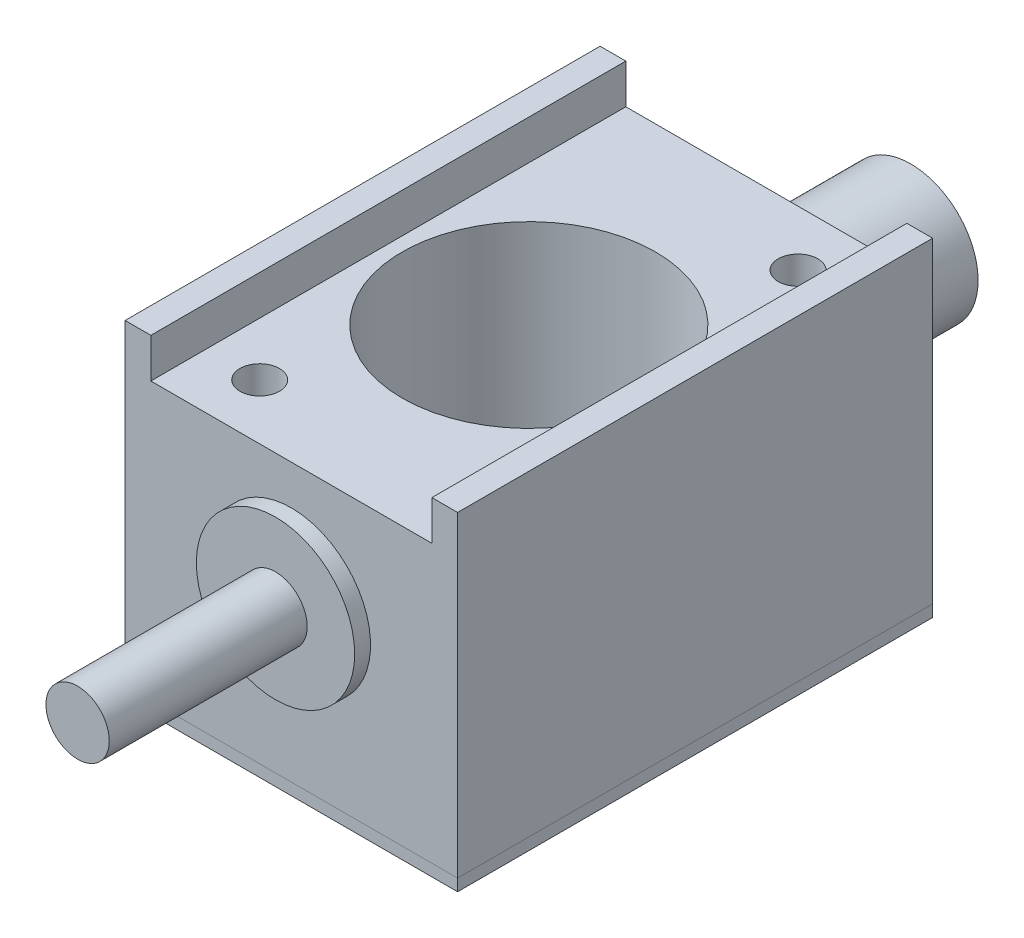
SolidWorks part; units mm, degrees
material "AISI 316 Annealed Stainless Steel Bar (SS)"
ref_plane "Front Plane" through (0, 0, 0) normal (0, 0, 1) x (1, 0, 0)
ref_plane "Top Plane" through (0, 0, 0) normal (0, 1, 0) x (1, 0, 0)
ref_plane "Right Plane" through (0, 0, 0) normal (1, 0, 0) x (0, 0, -1)
sketch "Sketch1" plane through (0, 0, 0) normal (0, 0, 1) x (1, 0, 0)
  line L1 (-21, -20) -> (21, -20)
  line L2 (-21, -20) -> (-21, 20)
  line L3 (-21, 20) -> (21, 20)
  line L4 (21, -20) -> (21, 20)
  line L5 (-21, -20) -> (21, 20) construction
  line L6 (-21, 20) -> (21, -20) construction
  point P0 (0, 0)
  dimension "D1" = 40
  dimension "D2" = 42
extrude "Boss-Extrude1" add sketch "Sketch1" along normal blind 60
sketch "Sketch2" plane through (0, 0, 60) normal (0, 0, 1) x (1, 0, 0)
  line L0 (21, -20) -> (21, 20) construction
  line L1 (-21, 20) -> (21, 20)
  line L2 (-21, 20) -> (-21, 15)
  line L3 (-21, 15) -> (21, 15)
  line L4 (21, 20) -> (21, 15)
  line L5 (17.75, 20) -> (17.75, 15)
  line L6 (-17.75, 20) -> (-17.75, 15)
  dimension "D1" = 5
  dimension "D2" = 3.25
  dimension "D3" = 3.25
extrude "Cut-Extrude1" cut sketch "Sketch2" against normal blind 60 contours L1 L6 L3 L5
sketch "Sketch3" plane through (0, 15, 0) normal (0, 1, 0) x (1, 0, 0)
  line L0 (-17.75, 0) -> (17.75, 0) construction
  circle A0 centre (0, -30) radius 16
  dimension "D1" = 32
  dimension "D2" = 30
extrude "Cut-Extrude2" cut sketch "Sketch3" against normal blind 40
sketch "Sketch4" plane through (0, 0, 0) normal (0, 0, -1) x (-1, 0, 0)
  circle A1 centre (0, 0) radius 8.5
  dimension "D2" = 17
extrude "Boss-Extrude2" add sketch "Sketch4" along normal blind 18.25
sketch "Sketch6" plane through (0, 0, 0) normal (0, 0, -1) x (-1, 0, 0)
  circle A0 centre (0, 0) radius 12.5
  dimension "D1" = 25
extrude "Boss-Extrude3" add sketch "Sketch6" along normal blind 2
sketch "Sketch7" plane through (0, 0, 60) normal (0, 0, 1) x (1, 0, 0)
  circle A0 centre (0, 0) radius 10
  dimension "D1" = 20
extrude "Boss-Extrude4" add sketch "Sketch7" along normal blind 2
sketch "Sketch8" plane through (0, 0, 62) normal (0, 0, 1) x (1, 0, 0)
  circle A0 centre (0, 0) radius 4
  dimension "D1" = 8
extrude "Boss-Extrude5" add sketch "Sketch8" along normal blind 25
sketch "Sketch9" plane through (0, 0, -18.25) normal (0, 0, -1) x (-1, 0, 0)
  circle A0 centre (0, 0) radius 2.5
  dimension "D1" = 5
extrude "Cut-Extrude6" cut sketch "Sketch9" against normal blind 32
sketch "Sketch10" plane through (0, -20, 0) normal (0, -1, 0) x (1, 0, 0)
  line L1 (-21, 60) -> (21, 60)
  line L2 (-21, 60) -> (-21, 0)
  line L3 (-21, 0) -> (21, 0)
  line L4 (21, 60) -> (21, 0)
  circle A0 centre (-11, 53) radius 2.5
  circle A1 centre (11, 7) radius 2.5
  circle A2 centre (0, 30) radius 11.2 construction
  circle A4 centre (0, 30) radius 6.75
  circle A5 centre (0, 40.7) radius 1.6
  circle A6 centre (0, 19.3) radius 1.6
  circle A7 centre (0, 30) radius 10.7 construction
  circle A8 centre (-11.2, 30) radius 1.55
  circle A9 centre (11.2, 30) radius 1.55
  dimension "D1" = 7
  dimension "D3" = 5
  dimension "D6" = 13.5
  dimension "D7" = 3.2
  dimension "D8" = 21.4
  dimension "D9" = 3.1
  dimension "D10" = 22.4
  dimension "D2" = 10
  dimension "D4" = 10
  dimension "D5" = 7
base flange "Base-Flange1" sketch "Sketch10" thickness 1.5 reverse thickness direction yes parameters "D1"=0.7366
sketch "Sketch15" plane through (0, -20, 0) normal (0, -1, 0) x (1, 0, 0)
  circle A0 centre (-11, 53) radius 2.5 construction
  circle A1 centre (11, 7) radius 2.5 construction
  circle A2 centre (-11, 53) radius 2.5
  circle A3 centre (11, 7) radius 2.5
extrude "Cut-Extrude7" cut sketch "Sketch15" against normal through all
sketch "Bend-Lines1" [suppressed] plane through (0, 0, 0) normal (0, 1, 0) x (1, 0, 0)
sketch "Bounding-Box1" [suppressed] plane through (0, 0, 0) normal (0, 1, 0) x (1, 0, 0)
sheet metal parameters "Sheet-Metal17" thickness 1.5 parameters "D1"=0.7366
flat pattern "Flat-Pattern17" [suppressed]
sketch "Bend-Lines2" plane through (0, 0, 0) normal (0, 1, 0) x (1, 0, 0)
sketch3d "Bounding-Box2" [suppressed]
  line L0 (-21, -60, 0) -> (-21, 0, 0) construction
  line L1 (21, -60, 0) -> (21, 0, 0) construction
  line L2 (-21, -60, 0) -> (21, -60, 0) construction
  line L3 (-21, 0, 0) -> (21, 0, 0) construction
